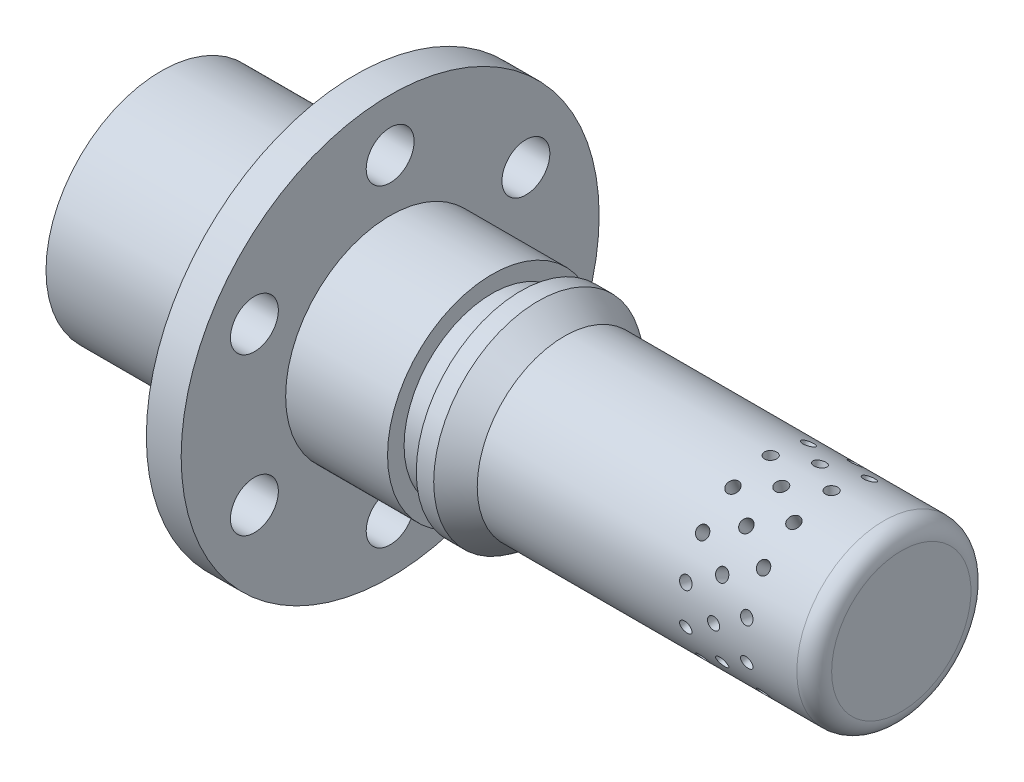
SolidWorks part; units mm, degrees
ref_plane "Front Plane" through (0, 0, 0) normal (0, 0, 1) x (1, 0, 0)
ref_plane "Top Plane" through (0, 0, 0) normal (0, 1, 0) x (1, 0, 0)
ref_plane "Right Plane" through (0, 0, 0) normal (1, 0, 0) x (0, 0, -1)
sketch "Sketch1" plane through (0, 0, 0) normal (0, 0, 1) x (1, 0, 0)
  line L0 (0, 0) -> (63.9348, 0) construction
  line L1 (0, 13.2205) -> (21.3, 13.2205)
  line L2 (46.3, 10) -> (83, 10)
  line L3 (85, 8) -> (85, 0)
  line L4 (46.3, 10) -> (43.3, 12)
  line L5 (41.3, 12) -> (41.3, 10.1)
  line L6 (41.3, 10.1) -> (38, 10.1)
  line L7 (38, 10.1) -> (38, 12)
  line L8 (26.3, 12) -> (26.3, 24)
  line L9 (26.3, 24) -> (22.3, 24)
  line L10 (22.3, 24) -> (22.3, 14.2205)
  line L11 (83, 0) -> (78.3812, 8)
  line L12 (0, 8) -> (78.3812, 8)
  line L13 (0, 13.2205) -> (0, 8)
  line L14 (41.3, 12) -> (43.3, 12)
  line L15 (26.3, 12) -> (38, 12)
  line L16 (83, 0) -> (85, 0)
  arc A0 (85, 8) -> (83, 10) centre (83, 8) ccw
  arc A1 (22.3, 14.2205) -> (21.3, 13.2205) centre (21.3, 14.2205) cw
  point P10 (85, 10)
  dimension "D3" = 2
  dimension "D18" = 1
  dimension "D1" = 10
  dimension "D2" = 38.7
  dimension "D4" = 3
  dimension "D5" = 13.2205
  dimension "D6" = 85
  dimension "D7" = 0
  dimension "D8" = 1.9
  dimension "D9" = 3.3
  dimension "D10" = 2
  dimension "D11" = 58.7
  dimension "D12" = 4
  dimension "D13" = 12
  dimension "D14" = 2
  dimension "D15" = 120
  dimension "D16" = 8
  dimension "D17" = 12
revolve "Revolve1" add sketch "Sketch1" angle 360 about L0
ref_plane "Plane1" through (0, 10, 0) normal (0, 1, 0) x (1, 0, 0)
sketch "Sketch2" plane through (0, 10, 0) normal (0, 1, 0) x (1, 0, 0)
  line L0 (0, 0) -> (85, 0) construction
  line L1 (85, -8) -> (85, 8) construction
  circle A0 centre (77, 0) radius 0.7
  circle A1 centre (70, 0) radius 0.7
  dimension "D1" = 8
  dimension "D2" = 1.4
  dimension "D3" = 7
extrude "Cut-Extrude1" cut sketch "Sketch2" against normal up to next
sketch "Sketch15" plane through (0, 0, 0) normal (0, 0, 1) x (1, 0, 0)
  circle A0 centre (73.4371, 0) radius 0.7
extrude "Cut-Extrude3" cut sketch "Sketch15" against normal through all
pattern_circular "CirPattern1" count 14 over 360 about axis through (83, 0, 0) along (-1, 0, 0) of "Cut-Extrude1", "Cut-Extrude3"
sketch "Sketch3" plane through (22.3, 0, 0) normal (-1, 0, 0) x (0, 0, 1)
  circle A0 centre (0, 0) radius 18 construction
  circle A1 centre (0, 18) radius 2.75
extrude "Cut-Extrude2" cut sketch "Sketch3" against normal up to next
pattern_circular "CirPattern2" count 6 over 360 about axis through (0, 0, 0) along (-1, 0, 0) of "Cut-Extrude2"
sketch "Sketch10" plane through (0, 0, 0) normal (0, 0, 1) x (1, 0, 0)
  line L2 (-1.814, 13.2205) -> (0, 13.2205)
  line L4 (-0.6861, 10.9721) -> (-1.3042, 12.4279)
  line L5 (0, 13.2205) -> (0, -13.2205) construction
  line L7 (21.3, 13.2205) -> (0, 13.2205) construction
  line L8 (-1.1278, 10.9717) -> (-0.4328, 12.2529)
  arc A3 (-1.814, 13.2205) -> (-0.4328, 12.2529) centre (-1.8141, 11.7508) cw
  arc A4 (0, 13.2205) -> (-1.3042, 12.4279) centre (0.0002, 11.7508) ccw
  arc A5 (-1.1278, 10.9717) -> (-0.6861, 10.9721) centre (-0.9071, 11.0872) ccw
  point P3 (-0.9263, 11.99)
  point P12 (-1.0849, 11.9997)
  point P24 (-0.907, 13.2205)
  dimension "D1" = 1.814
sketch "Sketch13" plane through (0, 0, 0) normal (-1, 0, 0) x (0, 0, 1)
  circle A0 centre (0, 0) radius 12
curve "Helix/Spiral1" [suppressed] pitch 1.8143 height 27.2143 turns 15
sweep "Cut-Sweep9" [suppressed] cut profiles "Sketch10" path "Helix/Spiral1"
